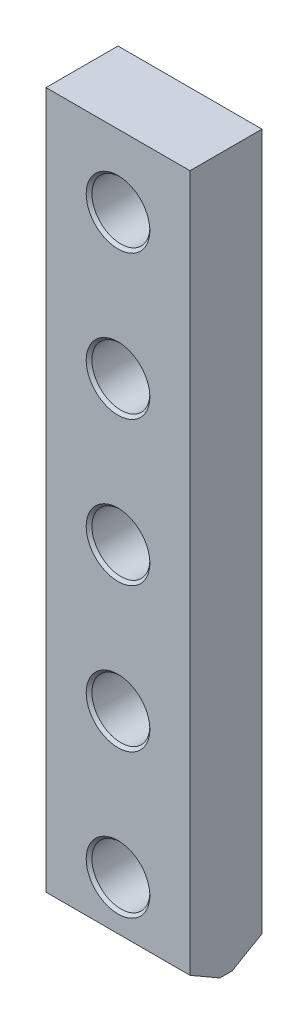
SolidWorks part; units mm, degrees
ref_plane "Спереди" through (0, 0, 0) normal (0, 0, 1) x (1, 0, 0)
ref_plane "Сверху" through (0, 0, 0) normal (0, 1, 0) x (1, 0, 0)
ref_plane "Справа" through (0, 0, 0) normal (1, 0, 0) x (0, 0, -1)
sketch "Эскиз1" plane through (0, 0, 0) normal (0, 0, 1) x (1, 0, 0)
  line L1 (0, 0) -> (50, 0)
  line L2 (0, 0) -> (0, 248)
  line L3 (0, 248) -> (50, 248)
  line L4 (50, 0) -> (50, 248)
  point P5 (25, 248)
  dimension "D1" = 248
  dimension "D2" = 50
extrude "Бобышка-Вытянуть1" add sketch "Эскиз1" along normal blind 25
sketch "Эскиз2" plane through (0, 0, 25) normal (0, 0, 1) x (1, 0, 0)
  line L0 (0, 0) -> (50, 0) construction
  line L1 (50, 0) -> (50, 248) construction
  circle A0 centre (25, 23) radius 10.05
  circle A1 centre (25, 73) radius 10.05
  circle A2 centre (25, 123) radius 10.05
  circle A3 centre (25, 173) radius 10.05
  circle A4 centre (25, 223) radius 10.05
  dimension "D1" = 5
  dimension "D2" = 23
  dimension "D3" = 25
  dimension "D4" = 20.1
extrude "Вырез-Вытянуть1" cut sketch "Эскиз2" against normal through all
chamfer "Фаска1" distance 6 angle 60 1 edges at (25, 0, 0) first distance on face at (35.05, 73, 0)
chamfer "Фаска2" distance 6 angle 60 1 edges at (25, 0, 25) first distance on face at (35.05, 73, 25)
chamfer "Фаска3" distance 1 angle 45 10 edges at (35.05, 223, 0) (35.05, 23, 0) (35.05, 73, 0) (35.05, 123, 0) (35.05, 173, 0) (35.05, 23, 25) (35.05, 73, 25) (35.05, 223, 25) (35.05, 173, 25) (35.05, 123, 25)
